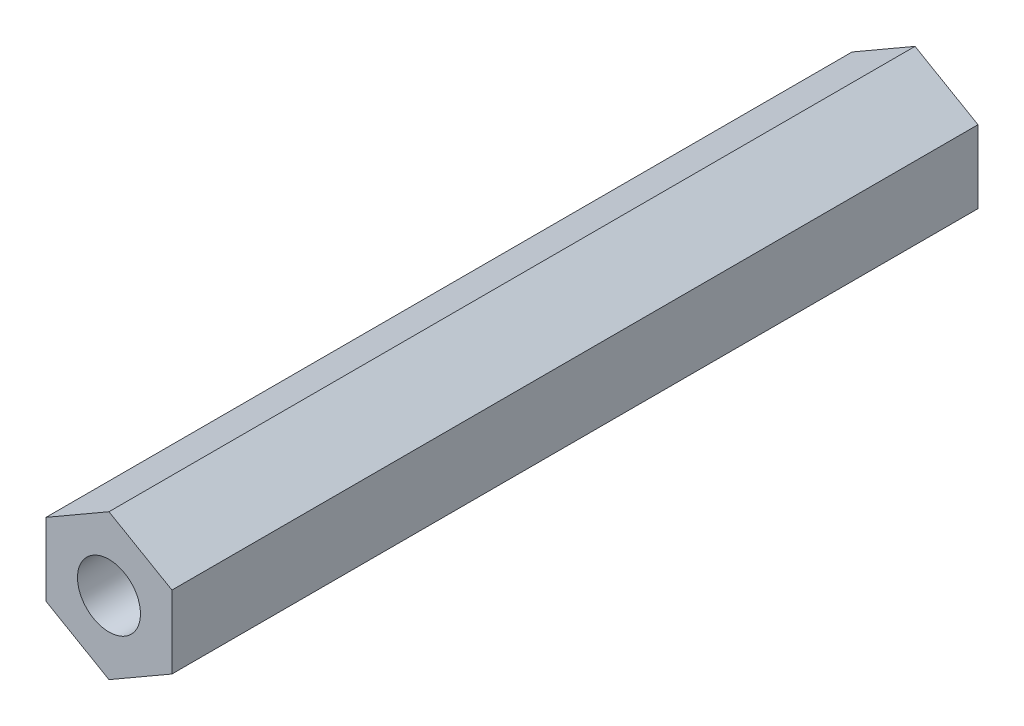
SolidWorks part; units mm, degrees
ref_plane "Płaszczyzna przednia" through (0, 0, 0) normal (0, 0, 1) x (1, 0, 0)
ref_plane "Płaszczyzna górna" through (0, 0, 0) normal (0, 1, 0) x (1, 0, 0)
ref_plane "Płaszczyzna prawa" through (0, 0, 0) normal (1, 0, 0) x (0, 0, -1)
sketch "Szkic1" plane through (0, 0, 0) normal (0, 0, 1) x (1, 0, 0)
  line L0 (0, 2.8868) -> (0, 0) construction
  line L1 (0, 2.8868) -> (-2.5, 1.4434)
  line L2 (-2.5, 1.4434) -> (-2.5, -1.4434)
  line L3 (-2.5, -1.4434) -> (0, -2.8868)
  line L4 (0, -2.8868) -> (2.5, -1.4434)
  line L5 (2.5, -1.4434) -> (2.5, 1.4434)
  line L6 (2.5, 1.4434) -> (0, 2.8868)
  circle A0 centre (0, 0) radius 2.5 construction
  dimension "D1" = 5
extrude "Dodanie-wyciągnięcie1" add sketch "Szkic1" along normal mid plane 32
hole_wizard "Otwór gwintowany M31" positions "Szkic3" profile "Szkic2" tap size "M3" standard "ISO"
sketch "Szkic3" plane through (0, 0, 16) normal (0, 0, 1) x (1, 0, 0)
  point P0 (0, 0)
sketch "Szkic2" plane through (0, 0, 16) normal (1, 0, 0) x (0, -1, 0)
  line L0 (0, 0) -> (0, 9.2511)
  line L1 (0, 9.2511) -> (1.25, 8.5)
  line L2 (1.25, 8.5) -> (1.25, 0)
  line L5 (1.25, 0) -> (0, 0)
  line L10 (0, 9.2511) -> (-1.25, 8.5) construction
  line L11 (0, -6.35) -> (0, 107.95) construction
  dimension "Średnica wiertła gwintu" = 2.5
  dimension "Głębokość otworu gwintowanego" = 8.5
  dimension "Kąt wiertła" = 118
cosmetic thread "Gwint otworu1" parameters "D1"=6, "D2"=3
mirror "Lustro1" about plane through (0, 0, 0) normal (0, 0, 1) of "Otwór gwintowany M31"
